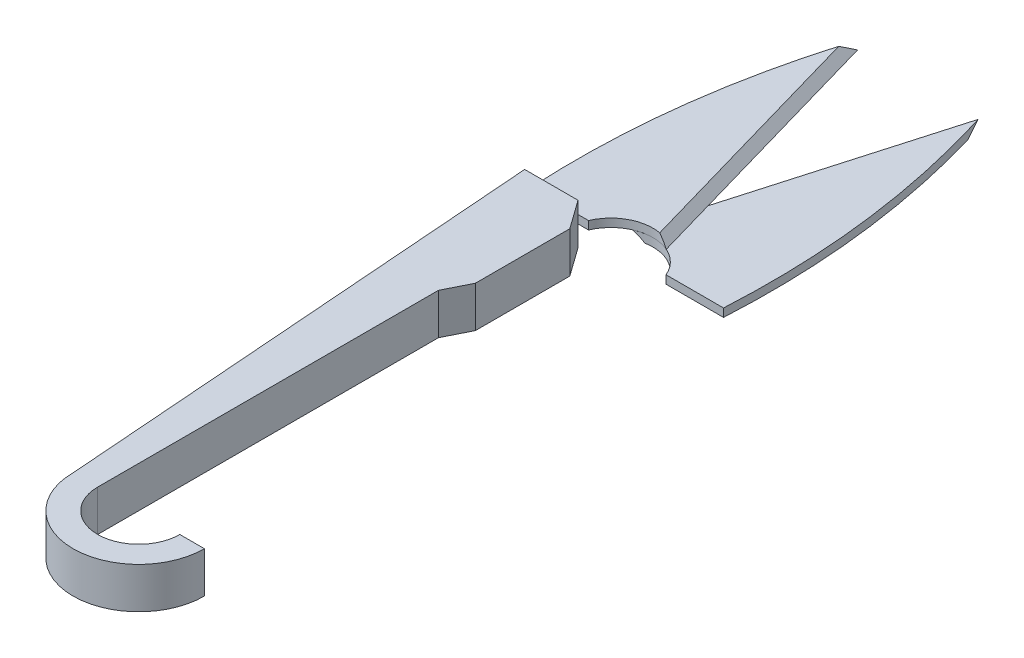
SolidWorks part; units mm, degrees
ref_plane "Front Plane" through (0, 0, 0) normal (0, 0, 1) x (1, 0, 0)
ref_plane "Top Plane" through (0, 0, 0) normal (0, 1, 0) x (1, 0, 0)
ref_plane "Right Plane" through (0, 0, 0) normal (1, 0, 0) x (0, 0, -1)
sketch "Sketch1" plane through (0, 0, 0) normal (0, 1, 0) x (1, 0, 0)
  line L0 (20.6846, -17.1912) -> (64.0461, 2.1146) construction
  line L1 (0, 52.5) -> (0, -52.5)
  line L2 (-12.5, 0) -> (12.5, 0) construction
  line L3 (0, 0) -> (0, 15)
  line L4 (-12.5, 15) -> (12.5, 15)
  line L5 (12.5, 15) -> (8, -44.5)
  line L6 (-12.5, 15) -> (-8, -44.5)
  line L7 (12.5, 15) -> (6, 15)
  line L8 (6, 15) -> (3.5, 11.5)
  line L9 (3.5, 11.5) -> (3.5, 0)
  line L10 (3.5, 0) -> (5, -3)
  line L11 (5, -3) -> (5, -44.5)
  line L12 (-5, -3) -> (-5, -44.5)
  line L13 (-3.5, 0) -> (-5, -3)
  line L14 (-3.5, 11.5) -> (-3.5, 0)
  line L15 (-6, 15) -> (-3.5, 11.5)
  line L16 (5, -44.5) -> (8, -44.5)
  circle A0 centre (0, -44.5) radius 8
  circle A1 centre (0, -44.5) radius 5
  point P6 (0, 0)
  point P10 (0, 0)
  point P18 (0, 15)
  dimension "D3" = 16
  dimension "D4" = 10
  dimension "D1" = 105
  dimension "D2" = 25
  dimension "D5" = 15
  dimension "D6" = 25
  dimension "D7" = 6.5
  dimension "D8" = 9
  dimension "D9" = 3.5
  dimension "D10" = 3
extrude "Boss-Extrude1" add sketch "Sketch1" along normal mid plane 5 contours A0 L12 L13 L14 L15 L4 L6 | A1 L12 A0 L1 | A1 L1 A0 L16 region at (-7.6248, 0, 8.2101) region at (-4.812, 0, 46.7322) region at (4.2115, 0, 48.7115)
sketch "Sketch3" plane through (0, 0, 0) normal (0, 1, 0) x (1, 0, 0)
  line L0 (-12.5, 15) -> (12.5, 15) construction
  line L1 (-7.3302, 50.3797) -> (2.0482, 17.6979)
  line L2 (0, 0) -> (0, 15) construction
  line L3 (0, 52.5) -> (0, -52.5) construction
  line L4 (-12.5, 0) -> (12.5, 0) construction
  line L5 (-11.7186, 15) -> (-4.7186, 15)
  line L6 (0, -55) -> (0, 55) construction
  line L7 (11.7186, 15) -> (4.7186, 15)
  line L8 (7.3302, 50.3797) -> (-2.0482, 17.6979)
  circle A0 centre (0, 13) radius 5.125
  spline S0 degree 2 poles (-11.7186, 15) (-12.7252, 33.0616) (-7.3302, 50.3797) knots 0 0 0 1 1 1
  spline S1 degree 2 poles (11.7186, 15) (12.7252, 33.0616) (7.3302, 50.3797) knots 0 0 0 1 1 1
  dimension "D1" = 13
  dimension "D3" = 7
extrude "Boss-Extrude2" add sketch "Sketch3" along normal blind 1 separate body contours S0 L5 A0 L8 L1 | A0 L1 L8 region at (-6.6942, 0, -28.6946) region at (0, 0, -20.2703)
extrude "Boss-Extrude3" add sketch "Sketch3<3>" against normal blind 1 separate body contours L7 S1 L8 L1 A0 | A0 L1 L8 region at (6.6942, 0, -28.6946) region at (0, 0, -20.2703)
sketch "Sketch3<3>" plane through (0, 0, 0) normal (0, 1, 0) x (1, 0, 0) same geometry as "Sketch3"
chamfer "Chamfer1" distance 1 angle 45 1 edges at (-2.641, 1, -34.0388)
chamfer "Chamfer2" distance 1 angle 45 1 edges at (2.641, -1, -34.0388)
